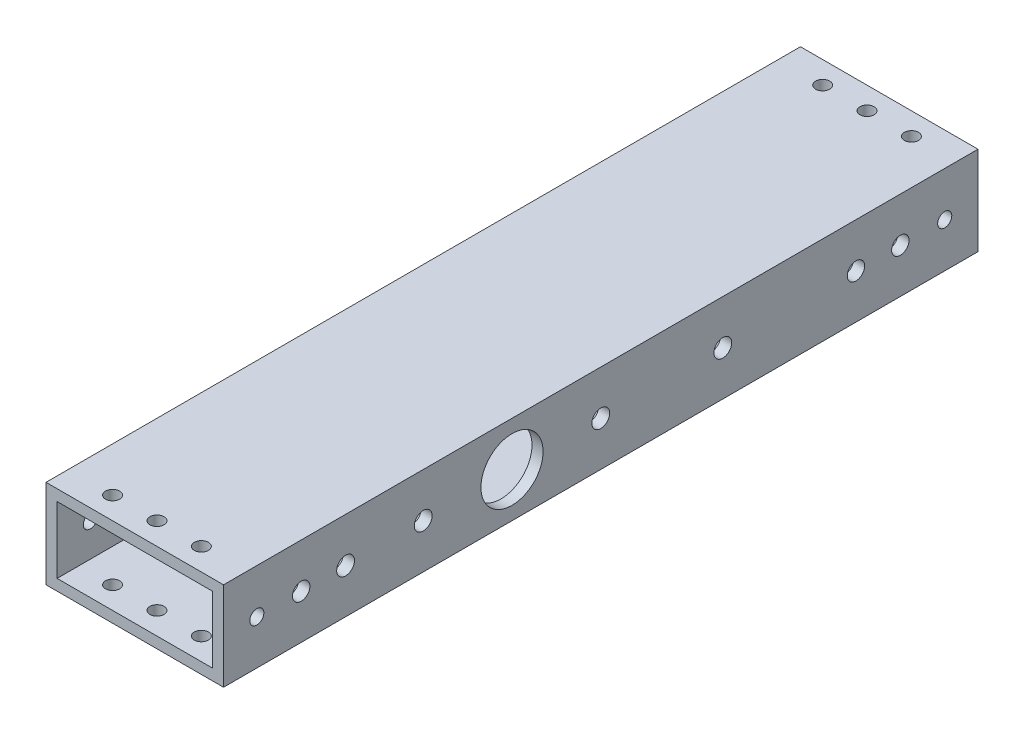
SolidWorks part; units mm, degrees
material "6061-T6 (SS)"
ref_plane "Front Plane" through (0, 0, 0) normal (0, 0, 1) x (1, 0, 0)
ref_plane "Top Plane" through (0, 0, 0) normal (0, 1, 0) x (1, 0, 0)
ref_plane "Right Plane" through (0, 0, 0) normal (1, 0, 0) x (0, 0, -1)
sketch "Sketch1" plane through (0, 0, 0) normal (0, 0, 1) x (1, 0, 0)
  line L0 (-22.225, 9.525) -> (22.225, 9.525)
  line L1 (-25.4, -12.7) -> (25.4, -12.7)
  line L2 (-25.4, -12.7) -> (-25.4, 12.7)
  line L3 (-25.4, 12.7) -> (25.4, 12.7)
  line L4 (25.4, -12.7) -> (25.4, 12.7)
  line L5 (-25.4, -12.7) -> (25.4, 12.7) construction
  line L6 (-25.4, 12.7) -> (25.4, -12.7) construction
  line L7 (22.225, -9.525) -> (22.225, 9.525)
  line L8 (-22.225, -9.525) -> (22.225, -9.525)
  line L9 (-22.225, -9.525) -> (-22.225, 9.525)
  point P0 (0, 0)
  dimension "D1" = 50.8
  dimension "D2" = 25.4
  dimension "D3" = 3.175
extrude "Boss-Extrude1" add sketch "Sketch1" along normal mid plane 215.9
sketch "Sketch2" plane through (25.4, 0, 0) normal (1, 0, 0) x (0, 0, -1)
  line L0 (-107.95, -12.7) -> (-107.95, 12.7) construction
  line L1 (0, 12.7) -> (0, -12.7) construction
  line L2 (-107.95, 12.7) -> (107.95, 12.7) construction
  line L3 (-107.95, -12.7) -> (107.95, -12.7) construction
  circle A0 centre (-98.425, 0) radius 2.0193
  circle A1 centre (98.425, 0) radius 2.0193
  circle A2 centre (-85.725, 0) radius 2.4892
  circle A3 centre (-73.025, 0) radius 2.4892
  circle A4 centre (73.025, 0) radius 2.4892
  circle A5 centre (85.725, 0) radius 2.4892
  dimension "D2" = 4.0386
  dimension "D5" = 4.9784
  dimension "D1" = 9.525
  dimension "D3" = 12.7
  dimension "D4" = 12.7
extrude "Cut-Extrude1" cut sketch "Sketch2" against normal through all
sketch "Sketch3" plane through (0, 12.7, 0) normal (0, 1, 0) x (1, 0, 0)
  line L0 (-25.4, 0) -> (25.4, 0) construction
  line L1 (-25.4, -107.95) -> (-25.4, 107.95) construction
  line L2 (25.4, -107.95) -> (25.4, 107.95) construction
  line L3 (25.4, -107.95) -> (-25.4, -107.95) construction
  circle A0 centre (-12.7, -101.6) radius 2.0193
  circle A1 centre (0, -101.6) radius 2.0193
  circle A2 centre (12.7, -101.6) radius 2.0193
  circle A3 centre (12.7, 101.6) radius 2.0193
  circle A4 centre (0, 101.6) radius 2.0193
  circle A5 centre (-12.7, 101.6) radius 2.0193
  dimension "D1" = 4.0386
  dimension "D2" = 12.7
  dimension "D3" = 12.7
  dimension "D4" = 6.35
extrude "Cut-Extrude2" cut sketch "Sketch3" against normal through all
sketch "Sketch4" plane through (25.4, 0, 0) normal (1, 0, 0) x (0, 0, -1)
  line L0 (-25.4, 0) -> (-73.025, 0) construction
  line L1 (-16.51, 0) -> (-34.29, 0) construction
  line L7 (-107.95, -12.7) -> (-107.95, 12.7) construction
  line L8 (-25.4, 0) -> (34.925, 0) construction
  line L9 (0, 12.7) -> (0, -12.7) construction
  line L10 (-107.95, 12.7) -> (107.95, 12.7) construction
  line L11 (-107.95, -12.7) -> (107.95, -12.7) construction
  line L12 (107.95, -12.7) -> (107.95, 12.7) construction
  circle A0 centre (-25.4, 0) radius 8.89
  circle A5 centre (-73.025, 0) radius 2.5527
  circle A7 centre (-73.025, 0) radius 2.4892 construction
  circle A9 centre (34.925, 0) radius 2.5527
  circle A10 centre (0, 0) radius 2.5527
  circle A11 centre (-50.8, 0) radius 2.5527
  point P25 (0, 0)
  dimension "D2" = 17.78
  dimension "D3" = 25.4
  dimension "D1" = 60.325
  dimension "D4" = 5.1054
  dimension "D5" = 25.4
  dimension "D6" = 25.4
extrude "Cut-Extrude3" cut sketch "Sketch4" against normal through all contours A0 | A5 | A9 | A11 | A10
sketch "Sketch5" plane through (0, -12.7, 0) normal (0, -1, 0) x (1, 0, 0)
  line L0 (-25.4, 107.95) -> (-25.4, -107.95) construction
  line L1 (-25.4, 107.95) -> (25.4, 107.95) construction
  line L2 (-16.51, -12.7) -> (-3.81, -12.7) construction
  line L3 (-16.51, -12.7) -> (-16.51, 0) construction
  circle A0 centre (-3.81, 63.5) radius 2.5527
  circle A1 centre (-16.51, 63.5) radius 2.5527
  circle A2 centre (-16.51, 50.8) radius 2.5527
  circle A3 centre (-3.81, 50.8) radius 2.5527
  circle A4 centre (-16.51, -12.7) radius 2.5527
  circle A5 centre (-3.81, -12.7) radius 2.5527
  circle A6 centre (-3.81, 0) radius 2.5527
  circle A7 centre (-16.51, 0) radius 2.5527
  dimension "D3" = 5.1054
  dimension "D4" = 8.89
  dimension "D7" = 12.7
  dimension "D12" = 50.8
  dimension "D5" = 44.45
  dimension "D6" = 12.7
  dimension "D10" = 12.7
  dimension "D11" = 12.7
  dimension "D1" = 2
  dimension "D2" = 2
  dimension "D8" = 2
  dimension "D9" = 2
extrude "Cut-Extrude4" cut sketch "Sketch5" against normal up to next
